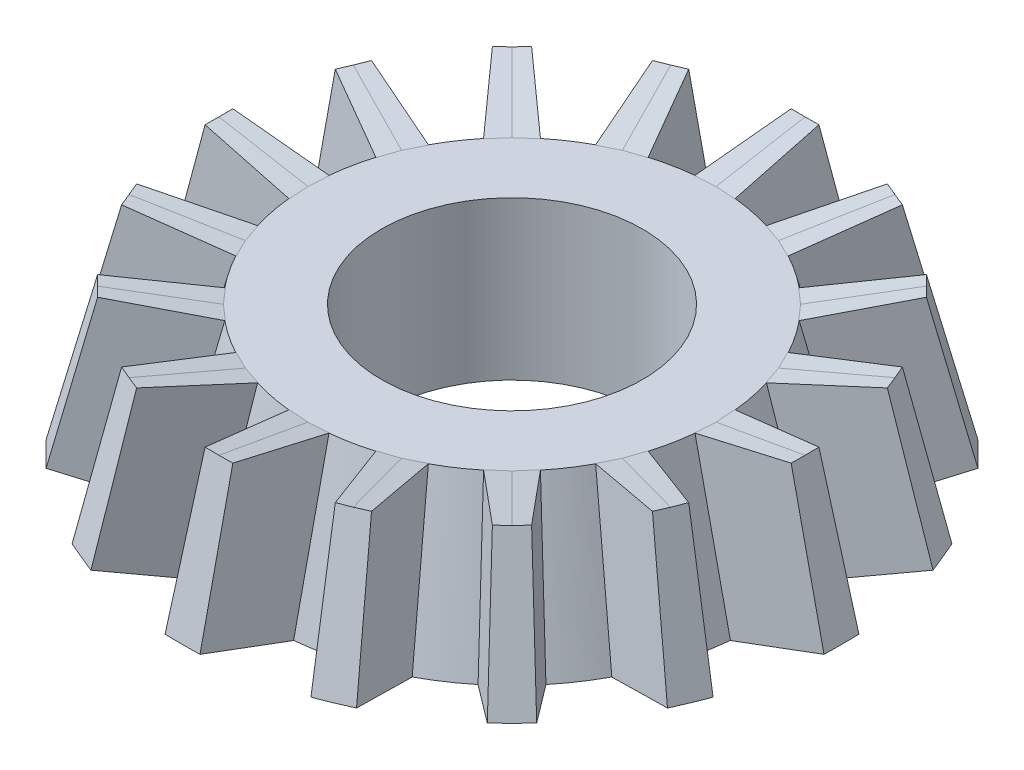
SolidWorks part; units mm, degrees
ref_plane "Front Plane" through (0, 0, 0) normal (0, 0, 1) x (1, 0, 0)
ref_plane "Top Plane" through (0, 0, 0) normal (0, 1, 0) x (1, 0, 0)
ref_plane "Right Plane" through (0, 0, 0) normal (1, 0, 0) x (0, 0, -1)
sketch "Sketch1" plane through (0, 0, 0) normal (0, 0, 1) x (1, 0, 0)
  line L0 (0, 0) -> (10.264, 0)
  line L1 (10.264, 0) -> (8.5998, 6.6551)
  line L2 (8.5998, 6.6551) -> (0, 6.6551)
  line L3 (0, 6.6551) -> (0, 0)
  dimension "D1" = 10.264
  dimension "D2" = 75.96
  dimension "D3" = 6.86
revolve "Revolve1" add sketch "Sketch1" angle 360 about L3
sketch "Sketch2" plane through (0, 0, 0) normal (0, 0, 1) x (1, 0, 0)
  line L0 (0, 0) -> (0, 67.611) construction
  line L1 (0, 67.611) -> (0, -92.6067) construction
sketch "Sketch3" plane through (0, 0, 0) normal (1, 0, 0) x (0, 0, -1)
  line L0 (-10.264, 0) -> (-8.5998, 6.6551) construction
  line L1 (-8.5998, 6.6551) -> (0, 41.0446) construction
  line L2 (0, 67.611) -> (0, -92.6067) construction
  line L3 (0, 41.0446) -> (-39.1729, -115.6035) construction
ref_plane "Plane1" through (0, 2.4157, 9.6599) normal (0, 0.2426, 0.9701) x (1, 0, 0)
sketch "Sketch8" plane through (0, 2.4157, 9.6599) normal (0, 0.2426, 0.9701) x (1, 0, 0)
  line L0 (0, 4.37) -> (0.8443, 4.38)
  line L1 (0.8443, 4.38) -> (1.0077, -2.478)
  line L2 (1.0077, -2.478) -> (0, -2.49)
  line L3 (0, -2.49) -> (-1.0077, -2.478)
  line L4 (-1.0077, -2.478) -> (-0.8443, 4.38)
  line L5 (-0.8443, 4.38) -> (0, 4.37)
  ellipse E0 centre (0, 6.4563) end of major axis (8.5998, 6.4563) minor radius 2.0863 construction
  ellipse E1 centre (0, 0) end of major axis (10.264, 0) minor radius 2.49 construction
  dimension "D1" = 1.0077
  dimension "D2" = 1.0077
  dimension "D3" = 0.8443
  dimension "D4" = 0.8443
extrude "Boss-Extrude1" add sketch "Sketch8" along normal blind 3.8 draft 4 and the other way blind 0.1 draft 4 other way draft outward yes
pattern_circular "CirPattern5" count 16 over 360 about axis through (0, 67.611, 0) along (0, -1, 0) of "Boss-Extrude1"
sketch "Sketch9" plane through (0, 6.6551, 0) normal (0, 1, 0) x (1, 0, 0)
  circle A0 centre (0, 0) radius 5.5
  dimension "D1" = 11
extrude "Cut-Extrude1" cut sketch "Sketch9" against normal blind 11.5
sketch "Sketch11" plane through (0, 0, 0) normal (0, -1, 0) x (1, 0, 0)
  circle A0 centre (0, 0) radius 13.97
extrude "Cut-Extrude4" cut sketch "Sketch11" along normal blind 10
sketch "Sketch10" plane through (0, 0, 0) normal (0, 1, 0) x (1, 0, 0)
  line L1 (-1.59, 1.59) -> (1.59, 1.59)
  line L2 (-1.59, 1.59) -> (-1.59, -1.59)
  line L3 (-1.59, -1.59) -> (1.59, -1.59)
  line L4 (1.59, 1.59) -> (1.59, -1.59)
  line L5 (-1.59, 1.59) -> (1.59, -1.59) construction
  line L6 (-1.59, -1.59) -> (1.59, 1.59) construction
  point P0 (0, 0)
  dimension "D1" = 3.18
  dimension "D2" = 3.18
